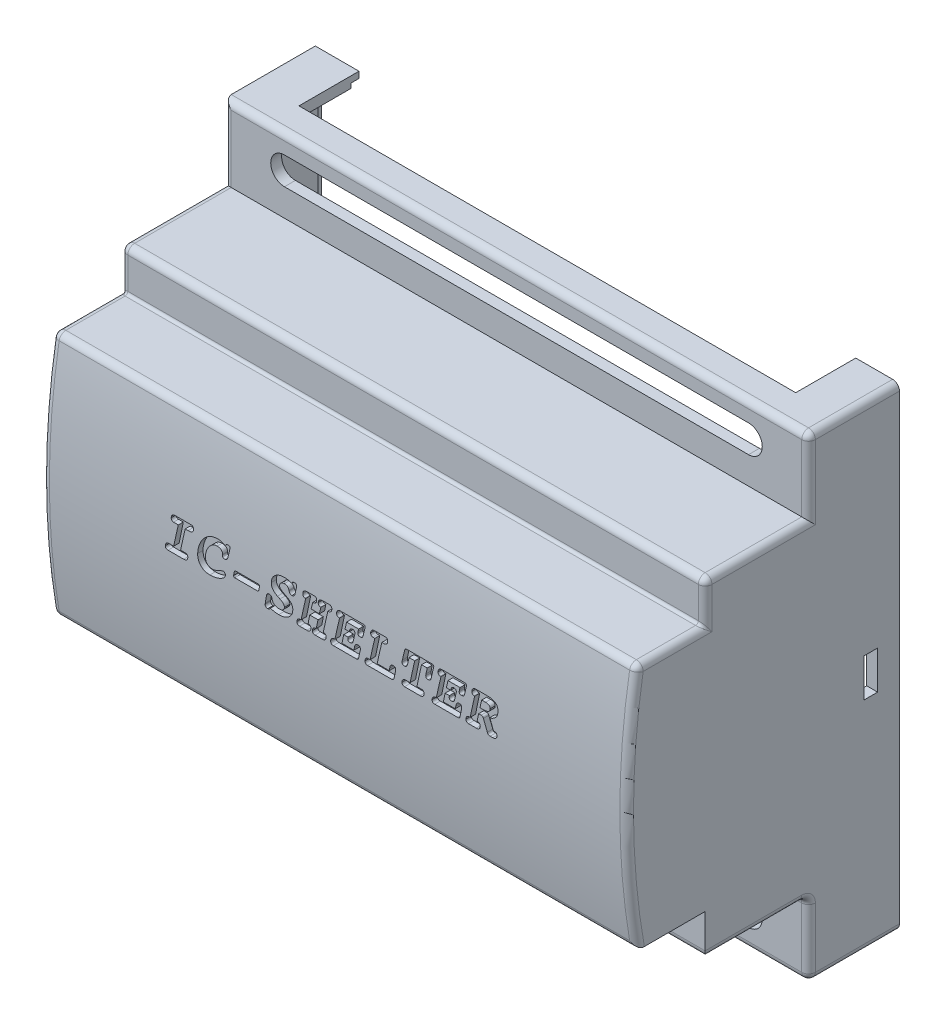
SolidWorks part; units mm, degrees
ref_plane "Alzado" through (0, 0, 0) normal (0, 0, 1) x (1, 0, 0)
ref_plane "Planta" through (0, 0, 0) normal (0, 1, 0) x (1, 0, 0)
ref_plane "Vista lateral" through (0, 0, 0) normal (1, 0, 0) x (0, 0, -1)
sketch "Sketch1" plane through (0, 0, 0) normal (1, 0, 0) x (0, 0, -1)
  line L0 (0, -43.5) -> (0, 43.5)
  line L1 (0, 43.5) -> (-16.65, 43.5)
  line L2 (-16.65, 43.5) -> (-16.65, 30)
  line L3 (-16.65, 30) -> (-35.59, 30)
  line L4 (-35.59, 30) -> (-35.59, 22.5)
  line L5 (-35.59, 22.5) -> (-48, 22.5)
  line L7 (55, 0) -> (-55, 0) construction
  line L8 (-35.59, -22.5) -> (-48, -22.5)
  line L9 (-35.59, -30) -> (-35.59, -22.5)
  line L10 (-16.65, -30) -> (-35.59, -30)
  line L11 (-16.65, -43.5) -> (-16.65, -30)
  line L12 (0, -43.5) -> (-16.65, -43.5)
  arc A1 (-48, 22.5) -> (-48, -22.5) centre (79.6725, 0) ccw
  point P12 (-48, 0)
  point P17 (0, 0)
  dimension "D7" = 259.28
  dimension "D1" = 87
  dimension "D2" = 16.65
  dimension "D3" = 35.59
  dimension "D4" = 48
  dimension "D5" = 60
  dimension "D6" = 45
extrude "Boss-Extrude3" add sketch "Sketch1" along normal blind 107
shell "Shell3" thickness 2 removed face at (53.5, 0, 0)
fillet "Fillet3" radius 1.25 26 edges at (107, 0, 49.9675) (53.5, -22.5, 48) (0, 0, 49.9675) (53.5, 22.5, 48) (107, -36.75, 16.65) (0, -36.75, 16.65) (53.5, -30, 35.59) (107, -30, 26.12) (53.5, -30, 16.65) (0, -30, 26.12) (0, -26.25, 35.59) (0, -22.5, 41.795) (0, 22.5, 41.795) (0, 26.25, 35.59) (0, 30, 26.12) (0, 36.75, 16.65) (53.5, 43.5, 16.65) (107, 43.5, 8.325) (107, 36.75, 16.65) (107, 30, 26.12) (53.5, 30, 35.59) (107, 26.25, 35.59) (107, 22.5, 41.795) (0, -43.5, 8.325) (107, -43.5, 8.325) (53.5, -43.5, 16.65)
sketch "Sketch5" plane through (107, 0, 0) normal (1, 0, 0) x (0, 0, -1)
  line L0 (0, 0) -> (-48.7175, 0) construction
  line L1 (0, -42.25) -> (0, 42.25) construction
  line L2 (-4, 3.5) -> (-6.5, 3.5)
  line L3 (-4, 3.5) -> (-4, -3.5)
  line L4 (-4, -3.5) -> (-6.5, -3.5)
  line L5 (-6.5, 3.5) -> (-6.5, -3.5)
  line L6 (-4, 3.5) -> (-6.5, -3.5) construction
  line L7 (-4, -3.5) -> (-6.5, 3.5) construction
  arc A0 (-46.9467, 21.25) -> (-46.7305, -22.5) centre (79.6725, 0) ccw construction
  point P7 (-5.25, 0)
  point P14 (-5.25, -3.5)
  dimension "D1" = 4
  dimension "D2" = 7
  dimension "D3" = 2.5
extrude "Cut-Extrude3" cut sketch "Sketch5" against normal through all
sketch "Sketch6" plane through (0, -43.5, 0) normal (0, -1, 0) x (1, 0, 0)
  line L0 (105.75, 0) -> (1.25, 0) construction
  line L1 (99, -11) -> (8, -11)
  line L2 (99, -11) -> (99, 11)
  line L3 (99, 11) -> (8, 11)
  line L4 (8, -11) -> (8, 11)
  line L5 (99, -11) -> (8, 11) construction
  line L6 (99, 11) -> (8, -11) construction
  point P0 (53.5, 0)
  dimension "D1" = 91
  dimension "D2" = 11
extrude "Cut-Extrude4" cut sketch "Sketch6" against normal through all
sketch "Sketch7" plane through (0, 0, 16.65) normal (0, 0, 1) x (1, 0, 0)
  line L0 (11, -37.5) -> (96, -37.5) construction
  line L1 (11, -35) -> (96, -35)
  line L2 (11, -40) -> (96, -40)
  line L3 (96, 37.52) -> (11, 37.52) construction
  line L4 (96, 35) -> (11, 35)
  line L5 (96, 40.04) -> (11, 40.04)
  line L6 (53.5, 42.25) -> (53.5, -43.5) construction
  line L7 (105.75, 42.25) -> (1.25, 42.25) construction
  line L8 (105.75, -43.5) -> (1.25, -43.5) construction
  arc A0 (11, -35) -> (11, -40) centre (11, -37.5) ccw
  arc A1 (96, -40) -> (96, -35) centre (96, -37.5) ccw
  arc A2 (96, 35) -> (96, 40.04) centre (96, 37.52) ccw
  arc A3 (11, 40.04) -> (11, 35) centre (11, 37.52) ccw
  point P2 (53.5, -37.5)
  point P10 (53.5, 37.52)
  dimension "D5" = 2.52
  dimension "D6" = 2.5
  dimension "D1" = 85
  dimension "D2" = 35
  dimension "D3" = 85
  dimension "D4" = 35
extrude "Cut-Extrude5" cut sketch "Sketch7" against normal blind 3
fillet "Fillet4" radius 0.5 30 edges at (2, -20.5, 39.9502) (2, -34.75, 14.65) (105, -20.5, 39.9502) (106.6339, 22.1339, 35.2239) (0.3661, 22.1339, 35.2239) (53.5, -20.5, 46.3105) (53.5, 20.5, 46.3105) (53.5, 22.5, 35.59) (53.5, 28, 33.59) (53.5, 28, 14.65) (105, 0, 47.9675) (105, 20.5, 39.9502) (105, 24.25, 33.59) (105, 28, 24.12) (105, 34.75, 14.65) (105, 41.5, 7.325) (2, 41.5, 7.325) (2, 34.75, 14.65) (2, 28, 24.12) (2, 24.25, 33.59) (2, 20.5, 39.9502) (2, 0, 47.9675) (2, -24.25, 33.59) (53.5, -28, 14.65) (105, -34.75, 14.65) (105, -28, 24.12) (105, -24.25, 33.59) (53.5, -28, 33.59) (2, -28, 24.12) (53.5, -20.5, 33.59)
sketch "Sketch8" plane through (0, -30, 0) normal (0, -1, 0) x (1, 0, 0)
  line L0 (107, 35.59) -> (1.25, 35.59) construction
  line L1 (6, 35.59) -> (8, 35.59)
  line L2 (6, 35.59) -> (6, 21.59)
  line L4 (8, 35.59) -> (8, 21.59)
  line L5 (8, 0) -> (1.25, 0) construction
  line L8 (53.5, 49.9675) -> (53.5, 0) construction
  line L9 (105.75, 49.9675) -> (1.25, 49.9675) construction
  line L10 (104.5, 0) -> (99, 0) construction
  line L11 (0, 17.9) -> (0, 34.34) construction
  line L12 (13, 35.59) -> (13, 21.59)
  line L13 (15, 35.59) -> (15, 21.59)
  line L14 (13, 35.59) -> (15, 35.59)
  line L15 (20, 35.59) -> (20, 21.59)
  line L16 (22, 35.59) -> (22, 21.59)
  line L17 (20, 35.59) -> (22, 35.59)
  line L18 (27, 35.59) -> (27, 21.59)
  line L19 (29, 35.59) -> (29, 21.59)
  line L20 (27, 35.59) -> (29, 35.59)
  line L21 (34, 35.59) -> (34, 21.59)
  line L22 (36, 35.59) -> (36, 21.59)
  line L23 (34, 35.59) -> (36, 35.59)
  line L24 (41, 35.59) -> (41, 21.59)
  line L25 (43, 35.59) -> (43, 21.59)
  line L26 (41, 35.59) -> (43, 35.59)
  line L27 (48, 35.59) -> (48, 21.59)
  line L28 (50, 35.59) -> (50, 21.59)
  line L29 (48, 35.59) -> (50, 35.59)
  line L30 (55, 35.59) -> (55, 21.59)
  line L31 (57, 35.59) -> (57, 21.59)
  line L32 (55, 35.59) -> (57, 35.59)
  line L33 (62, 35.59) -> (62, 21.59)
  line L34 (64, 35.59) -> (64, 21.59)
  line L35 (62, 35.59) -> (64, 35.59)
  line L36 (69, 35.59) -> (69, 21.59)
  line L37 (71, 35.59) -> (71, 21.59)
  line L38 (69, 35.59) -> (71, 35.59)
  line L39 (76, 35.59) -> (76, 21.59)
  line L40 (78, 35.59) -> (78, 21.59)
  line L41 (76, 35.59) -> (78, 35.59)
  line L42 (83, 35.59) -> (83, 21.59)
  line L43 (85, 35.59) -> (85, 21.59)
  line L44 (83, 35.59) -> (85, 35.59)
  line L45 (90, 35.59) -> (90, 21.59)
  line L46 (92, 35.59) -> (92, 21.59)
  line L47 (90, 35.59) -> (92, 35.59)
  line L48 (97, 35.59) -> (97, 21.59)
  line L49 (99, 35.59) -> (99, 21.59)
  line L50 (97, 35.59) -> (99, 35.59)
  arc A0 (6, 21.59) -> (8, 21.59) centre (7, 21.59) ccw
  arc A1 (13, 21.59) -> (15, 21.59) centre (14, 21.59) ccw
  arc A2 (20, 21.59) -> (22, 21.59) centre (21, 21.59) ccw
  arc A3 (27, 21.59) -> (29, 21.59) centre (28, 21.59) ccw
  arc A4 (34, 21.59) -> (36, 21.59) centre (35, 21.59) ccw
  arc A5 (41, 21.59) -> (43, 21.59) centre (42, 21.59) ccw
  arc A6 (48, 21.59) -> (50, 21.59) centre (49, 21.59) ccw
  arc A7 (55, 21.59) -> (57, 21.59) centre (56, 21.59) ccw
  arc A8 (62, 21.59) -> (64, 21.59) centre (63, 21.59) ccw
  arc A9 (69, 21.59) -> (71, 21.59) centre (70, 21.59) ccw
  arc A10 (76, 21.59) -> (78, 21.59) centre (77, 21.59) ccw
  arc A11 (83, 21.59) -> (85, 21.59) centre (84, 21.59) ccw
  arc A12 (90, 21.59) -> (92, 21.59) centre (91, 21.59) ccw
  arc A13 (97, 21.59) -> (99, 21.59) centre (98, 21.59) ccw
  point P17 (6, 28.59)
  dimension "D1" = 1
  dimension "D2" = 21.59
  dimension "D3" = 6
  dimension "D4" = 14
sketch "Sketch10" plane through (0, 0, 0) normal (0, 0, -1) x (-1, 0, 0)
  line L8 (-107, -42.25) -> (-107, 42.25) construction
  line L9 (-105.85, 42.35) -> (-1.15, 42.35)
  line L10 (-105.85, 42.35) -> (-105.85, -42.35)
  line L11 (-105.85, -42.35) -> (-1.15, -42.35)
  line L12 (-1.15, 42.35) -> (-1.15, -42.35)
  line L13 (0, -42.25) -> (0, 43.5) construction
  line L14 (-105.75, 43.5) -> (-99, 43.5) construction
  line L15 (-105.75, -43.5) -> (-99, -43.5) construction
  dimension "D1" = 1.15
  dimension "D2" = 1.15
  dimension "D3" = 1.15
  dimension "D4" = 1.15
extrude "Cut-Extrude8" cut sketch "Sketch10" against normal blind 1.5
fillet "Fillet5" radius 0.5 7 edges at (105, -41.5, 7.825) (104.8536, -41.5, 14.5036) (53.5, -41.5, 14.65) (2.1464, -41.5, 14.5036) (1.15, -42.35, 0.75) (2, -41.5, 7.825) (105.85, -42.35, 0.75)
ref_plane "Plane1" through (0, 0, 49.9675) normal (0, 0, 1) x (1, 0, 0)
sketch "Sketch11" plane through (0, 0, 49.9675) normal (0, 0, 1) x (1, 0, 0)
  line L0 (0, 0) -> (105.75, 0) construction
  line L1 (105.75, -21.4569) -> (105.75, 21.4569) construction
  text T0 "IC-SHELTER" font "Courier10 BT" height 6
extrude "Cut-Extrude9" cut sketch "Sketch11" against normal blind 1
